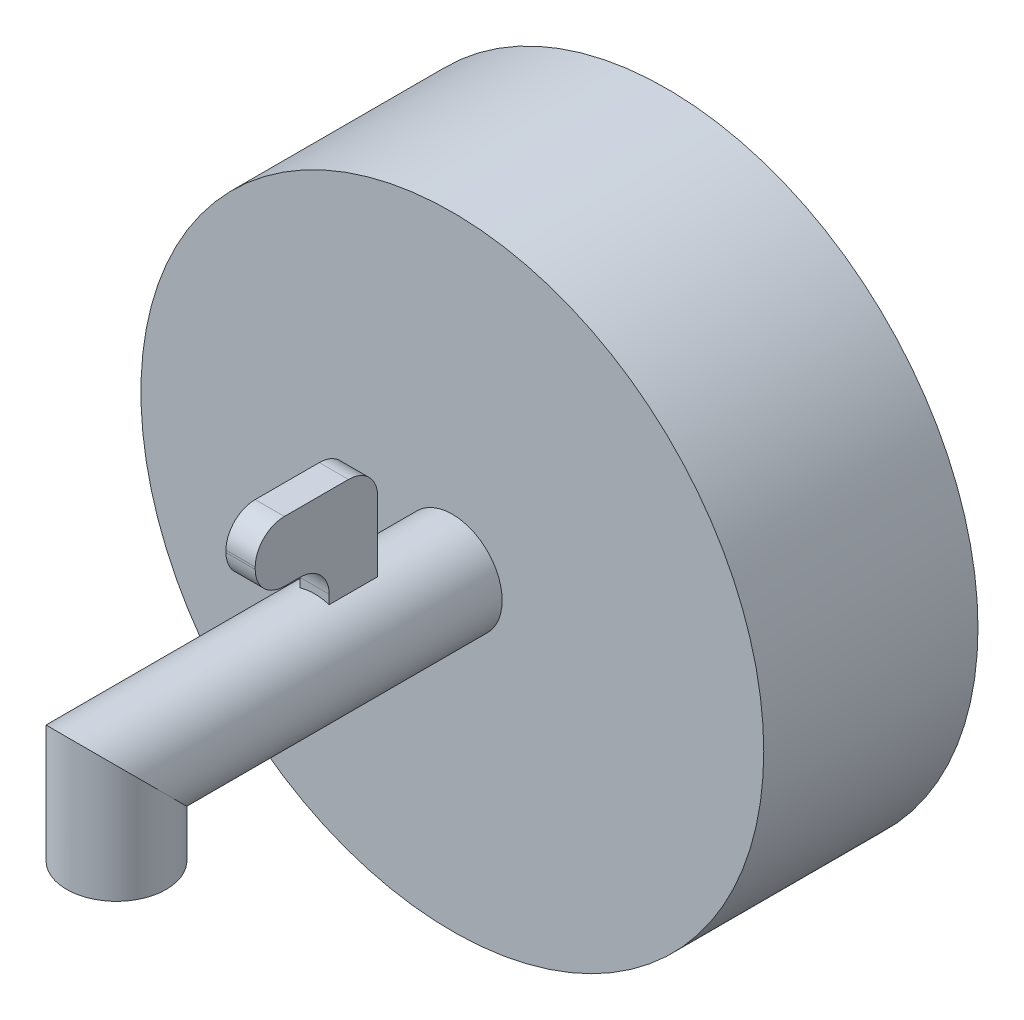
SolidWorks part; units mm, degrees
material "CA"
ref_plane "Front Plane" through (0, 0, 0) normal (0, 0, 1) x (1, 0, 0)
ref_plane "Top Plane" through (0, 0, 0) normal (0, 1, 0) x (1, 0, 0)
ref_plane "Right Plane" through (0, 0, 0) normal (1, 0, 0) x (0, 0, -1)
sketch "Sketch1" plane through (0, 0, 0) normal (0, 0, 1) x (1, 0, 0)
  circle A0 centre (0, 0) radius 25.45
  circle A1 centre (0, 0) radius 31.9809
  dimension "D1" = 50.9
extrude "Boss-Extrude1" add sketch "Sketch1" along normal blind 20
sketch "Sketch2" plane through (0, 0, 20) normal (0, 0, 1) x (1, 0, 0)
  circle A0 centre (0, 0) radius 31.9809
  point P3 (0, 0)
extrude "Boss-Extrude2" add sketch "Sketch2" along normal blind 2
sketch "Sketch3" plane through (0, 0, 22) normal (0, 0, 1) x (1, 0, 0)
  circle A0 centre (0, 0) radius 5.1144
sketch "Sketch4" plane through (0, 0, 0) normal (1, 0, 0) x (0, 0, -1)
  line L0 (-22, 0) -> (-56.4962, 0)
  line L1 (-56.4962, 0) -> (-56.4962, -8.4546)
sweep "Sweep2" add profiles "Sketch3" path "Sketch4"
sketch "Sketch5" plane through (0, 0, 0) normal (1, 0, 0) x (0, 0, -1)
  line L0 (-36.1501, 0) -> (-36.1501, 5.8238)
  line L1 (-39.1501, 8.8238) -> (-40.7462, 8.8238)
  line L2 (-43.7462, 11.8238) -> (-43.7462, 12.0388)
  line L3 (-40.7462, 15.0388) -> (-34.1627, 15.0388)
  line L4 (-31.1627, 12.0388) -> (-31.1627, 0)
  line L5 (-31.1627, 0) -> (-36.1501, 0)
  arc A0 (-43.7462, 12.0388) -> (-40.7462, 15.0388) centre (-40.7462, 12.0388) cw
  arc A1 (-34.1627, 15.0388) -> (-31.1627, 12.0388) centre (-34.1627, 12.0388) cw
  arc A2 (-36.1501, 5.8238) -> (-39.1501, 8.8238) centre (-39.1501, 5.8238) ccw
  arc A3 (-40.7462, 8.8238) -> (-43.7462, 11.8238) centre (-40.7462, 11.8238) cw
  point P12 (-43.7462, 8.8238)
  dimension "D1" = 3
  dimension "D2" = 3
  dimension "D3" = 3
  dimension "D4" = 3
extrude "Boss-Extrude3" add sketch "Sketch5" along normal blind 1.5 and the other way blind 1.5
